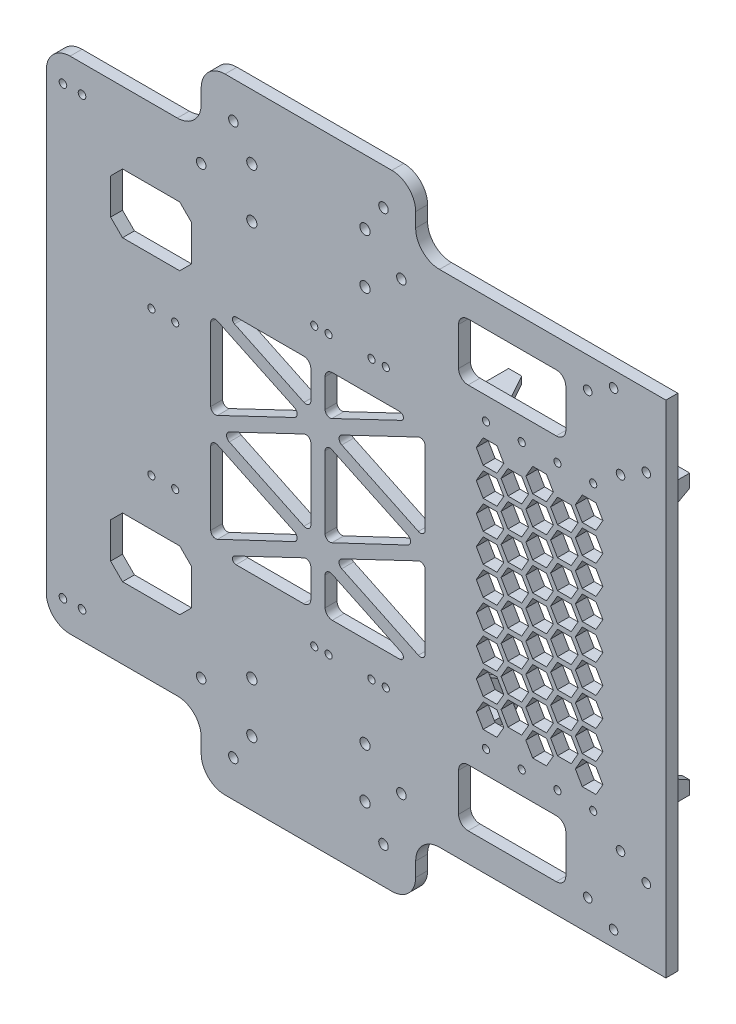
SolidWorks part; units mm, degrees
ref_plane "前视基准面" through (0, 0, 0) normal (0, 0, 1) x (1, 0, 0)
ref_plane "上视基准面" through (0, 0, 0) normal (0, 1, 0) x (1, 0, 0)
ref_plane "右视基准面" through (0, 0, 0) normal (1, 0, 0) x (0, 0, -1)
sketch "草图1" plane through (0, 0, 0) normal (0, 0, 1) x (1, 0, 0)
  line L2 (-130, 95) -> (-130, -95)
  line L3 (-120, -105) -> (-75, -105)
  line L4 (130, 95) -> (130, -95)
  line L5 (126.7518, 102.3765) -> (130, 105) construction
  line L6 (-130, -105) -> (-126.7518, -102.3765) construction
  line L9 (-65, -115) -> (-65, -121)
  line L10 (-55, -131) -> (15, -131)
  line L11 (25, -121) -> (25, -115)
  line L13 (35, -105) -> (120, -105)
  line L14 (126.7518, -102.3765) -> (130, -105) construction
  line L15 (-130, 105) -> (-126.7518, 102.3765) construction
  line L16 (-130, 0) -> (130, 0) construction
  line L17 (35, 105) -> (120, 105)
  line L18 (25, 121) -> (25, 115)
  line L19 (-55, 131) -> (15, 131)
  line L20 (-65, 115) -> (-65, 121)
  line L21 (-120, 105) -> (-75, 105)
  arc A1 (-120, -105) -> (-130, -95) centre (-120, -95) cw
  arc A3 (120, -105) -> (130, -95) centre (120, -95) ccw
  arc A8 (-65, -115) -> (-75, -105) centre (-75, -115) ccw
  arc A9 (25, -115) -> (35, -105) centre (35, -115) cw
  arc A10 (-55, -131) -> (-65, -121) centre (-55, -121) cw
  arc A11 (15, -131) -> (25, -121) centre (15, -121) ccw
  arc A12 (15, 131) -> (25, 121) centre (15, 121) cw
  arc A13 (-55, 131) -> (-65, 121) centre (-55, 121) ccw
  arc A14 (25, 115) -> (35, 105) centre (35, 115) ccw
  arc A15 (-65, 115) -> (-75, 105) centre (-75, 115) cw
  arc A16 (120, 105) -> (130, 95) centre (120, 95) cw
  arc A17 (-120, 105) -> (-130, 95) centre (-120, 95) ccw
  point P0 (0, 0)
  point P40 (25, -105)
  point P45 (25, 105)
  dimension "D2" = 10
  dimension "D3" = 65
  dimension "D4" = 10
  dimension "D5" = 105
  dimension "D7" = 10
  dimension "D8" = 10
  dimension "D10" = 10
  dimension "D12" = 10
  dimension "D13" = 105
  dimension "D18" = 90
  dimension "D19" = 6
extrude "凸台-拉伸1" add sketch "草图1" along normal blind 5
sketch "草图4" plane through (0, 0, 0) normal (0, 0, -1) x (-1, 0, 0)
  line L0 (-39, -47.5) -> (-39, -58.5)
  line L1 (-39, -58.5) -> (-50, -58.5)
  line L2 (-50, -58.5) -> (-50, -55.5)
  line L3 (-50, -55.5) -> (-42, -55.5)
  line L4 (-42, -55.5) -> (-42, -47.5)
  line L5 (-42, -47.5) -> (-39, -47.5)
  line L6 (-130, 0) -> (-25.5592, 0) construction
  line L7 (-130, -95) -> (-130, 95) construction
  line L10 (-130, -95) -> (-130, 95) construction
  dimension "D1" = 11
  dimension "D2" = 11
  dimension "D3" = 3
  dimension "D4" = 3
  dimension "D5" = 80
  dimension "D7" = 55.5
extrude "凸台-拉伸2" add sketch "草图4" along normal blind 20
sketch "草图5" plane through (0, -58.5, 0) normal (0, -1, 0) x (1, 0, 0)
  line L0 (50, -10) -> (44.5, -20)
  line L1 (50, -20) -> (50, 0) construction
  line L2 (50, -20) -> (39, -20) construction
  line L3 (44.5, -20) -> (50, -20)
  line L4 (50, -20) -> (50, -10)
  dimension "D1" = 10
  dimension "D2" = 5.5
extrude "切除-拉伸3" cut sketch "草图5" against normal blind 10
sketch "草图6" plane through (39, 0, 0) normal (-1, 0, 0) x (0, 0, 1)
  line L0 (-20, -53) -> (-10, -47.5)
  line L1 (-20, -58.5) -> (-20, -47.5) construction
  line L2 (-20, -47.5) -> (0, -47.5) construction
  line L3 (-10, -47.5) -> (-20, -47.5)
  line L4 (-20, -47.5) -> (-20, -53)
  dimension "D1" = 10
  dimension "D2" = 5.5
extrude "切除-拉伸4" cut sketch "草图6" against normal blind 10
ref_plane "基准面2" through (77, 0, 0) normal (1, 0, 0) x (0, 0, -1)
mirror "镜向1" about plane through (77, 0, 0) normal (1, 0, 0) of "凸台-拉伸2", "切除-拉伸4", "切除-拉伸3"
mirror "镜向2" about plane through (0, 0, 0) normal (0, 1, 0) of "镜向1"
sketch "草图7" plane through (0, 0, 0) normal (0, 0, -1) x (-1, 0, 0)
  line L4 (-112, -55.5) -> (-104, -55.5) construction
  line L5 (-112, 47.5) -> (-112, 55.5) construction
  line L6 (-112, 55.5) -> (-104, 55.5) construction
  line L7 (-92.013, 36) -> (-94.8997, 41)
  line L8 (-94.8997, 41) -> (-100.6732, 41)
  line L9 (-100.6732, 41) -> (-103.56, 36)
  line L10 (-103.56, 36) -> (-100.6732, 31)
  line L11 (-100.6732, 31) -> (-94.8997, 31)
  line L12 (-94.8997, 31) -> (-92.013, 36)
  line L13 (-77.0019, 36) -> (-97.7865, 36) construction
  line L14 (-74.1151, 31) -> (-71.2284, 36)
  line L15 (-71.2284, 36) -> (-74.1151, 41)
  line L16 (-74.1151, 41) -> (-79.8886, 41)
  line L17 (-79.8886, 41) -> (-82.7754, 36)
  line L18 (-82.7754, 36) -> (-79.8886, 31)
  line L19 (-79.8886, 31) -> (-74.1151, 31)
  line L20 (-92.013, 24) -> (-94.8997, 29)
  line L21 (-93.1677, 30) -> (-90.2809, 25)
  line L22 (-90.2809, 25) -> (-84.5074, 25)
  line L23 (-84.5074, 25) -> (-81.6207, 30)
  line L24 (-81.6207, 30) -> (-84.5074, 35)
  line L25 (-84.5074, 35) -> (-90.2809, 35)
  line L26 (-90.2809, 35) -> (-93.1677, 30)
  line L27 (-84.5074, 37) -> (-81.6207, 42)
  line L28 (-81.6207, 42) -> (-84.5074, 47)
  line L29 (-84.5074, 47) -> (-90.2809, 47)
  line L30 (-90.2809, 47) -> (-93.1677, 42)
  line L31 (-93.1677, 42) -> (-90.2809, 37)
  line L32 (-90.2809, 37) -> (-84.5074, 37)
  line L33 (-79.8886, 43) -> (-74.1151, 43)
  line L34 (-74.1151, 43) -> (-71.2284, 48)
  line L35 (-71.2284, 48) -> (-74.1151, 53)
  line L36 (-74.1151, 53) -> (-79.8886, 53)
  line L37 (-79.8886, 53) -> (-82.7754, 48)
  line L38 (-82.7754, 48) -> (-79.8886, 43)
  line L39 (-94.8997, 43) -> (-92.013, 48)
  line L40 (-92.013, 48) -> (-94.8997, 53)
  line L41 (-94.8997, 53) -> (-100.6732, 53)
  line L42 (-100.6732, 53) -> (-103.56, 48)
  line L43 (-103.56, 48) -> (-100.6732, 43)
  line L44 (-100.6732, 43) -> (-94.8997, 43)
  line L45 (-72.3831, 42) -> (-69.4963, 37)
  line L46 (-69.4963, 37) -> (-63.7228, 37)
  line L47 (-63.7228, 37) -> (-60.8361, 42)
  line L48 (-60.8361, 42) -> (-63.7228, 47)
  line L49 (-63.7228, 47) -> (-69.4963, 47)
  line L50 (-69.4963, 47) -> (-72.3831, 42)
  line L51 (-94.8997, 29) -> (-100.6732, 29)
  line L52 (-100.6732, 29) -> (-103.56, 24)
  line L53 (-103.56, 24) -> (-100.6732, 19)
  line L54 (-100.6732, 19) -> (-94.8997, 19)
  line L55 (-94.8997, 19) -> (-92.013, 24)
  line L56 (-93.1677, 18) -> (-90.2809, 13)
  line L57 (-90.2809, 13) -> (-84.5074, 13)
  line L58 (-84.5074, 13) -> (-81.6207, 18)
  line L59 (-81.6207, 18) -> (-84.5074, 23)
  line L60 (-84.5074, 23) -> (-90.2809, 23)
  line L61 (-90.2809, 23) -> (-93.1677, 18)
  line L62 (-74.1151, 19) -> (-71.2284, 24)
  line L63 (-71.2284, 24) -> (-74.1151, 29)
  line L64 (-74.1151, 29) -> (-79.8886, 29)
  line L65 (-79.8886, 29) -> (-82.7754, 24)
  line L66 (-82.7754, 24) -> (-79.8886, 19)
  line L67 (-79.8886, 19) -> (-74.1151, 19)
  line L68 (-72.3831, 30) -> (-69.4963, 25)
  line L69 (-69.4963, 25) -> (-63.7228, 25)
  line L70 (-63.7228, 25) -> (-60.8361, 30)
  line L71 (-60.8361, 30) -> (-63.7228, 35)
  line L72 (-63.7228, 35) -> (-69.4963, 35)
  line L73 (-69.4963, 35) -> (-72.3831, 30)
  line L74 (-92.013, 12) -> (-94.8997, 17)
  line L75 (-94.8997, 17) -> (-100.6732, 17)
  line L76 (-100.6732, 17) -> (-103.56, 12)
  line L77 (-103.56, 12) -> (-100.6732, 7)
  line L78 (-100.6732, 7) -> (-94.8997, 7)
  line L79 (-94.8997, 7) -> (-92.013, 12)
  line L80 (-93.1677, 6) -> (-90.2809, 1)
  line L81 (-90.2809, 1) -> (-84.5074, 1)
  line L82 (-84.5074, 1) -> (-81.6207, 6)
  line L83 (-81.6207, 6) -> (-84.5074, 11)
  line L84 (-84.5074, 11) -> (-90.2809, 11)
  line L85 (-90.2809, 11) -> (-93.1677, 6)
  line L86 (-74.1151, 7) -> (-71.2284, 12)
  line L87 (-71.2284, 12) -> (-74.1151, 17)
  line L88 (-74.1151, 17) -> (-79.8886, 17)
  line L89 (-79.8886, 17) -> (-82.7754, 12)
  line L90 (-82.7754, 12) -> (-79.8886, 7)
  line L91 (-79.8886, 7) -> (-74.1151, 7)
  line L92 (-72.3831, 18) -> (-69.4963, 13)
  line L93 (-69.4963, 13) -> (-63.7228, 13)
  line L94 (-63.7228, 13) -> (-60.8361, 18)
  line L95 (-60.8361, 18) -> (-63.7228, 23)
  line L96 (-63.7228, 23) -> (-69.4963, 23)
  line L97 (-69.4963, 23) -> (-72.3831, 18)
  line L98 (-92.013, 0) -> (-94.8997, 5)
  line L99 (-94.8997, 5) -> (-100.6732, 5)
  line L100 (-100.6732, 5) -> (-103.56, 0)
  line L101 (-103.56, 0) -> (-100.6732, -5)
  line L102 (-100.6732, -5) -> (-94.8997, -5)
  line L103 (-94.8997, -5) -> (-92.013, 0)
  line L104 (-93.1677, -6) -> (-90.2809, -11)
  line L105 (-90.2809, -11) -> (-84.5074, -11)
  line L106 (-84.5074, -11) -> (-81.6207, -6)
  line L107 (-81.6207, -6) -> (-84.5074, -1)
  line L108 (-84.5074, -1) -> (-90.2809, -1)
  line L109 (-90.2809, -1) -> (-93.1677, -6)
  line L110 (-74.1151, -5) -> (-71.2284, 0)
  line L111 (-71.2284, 0) -> (-74.1151, 5)
  line L112 (-74.1151, 5) -> (-79.8886, 5)
  line L113 (-79.8886, 5) -> (-82.7754, 0)
  line L114 (-82.7754, 0) -> (-79.8886, -5)
  line L115 (-79.8886, -5) -> (-74.1151, -5)
  line L116 (-72.3831, 6) -> (-69.4963, 1)
  line L117 (-69.4963, 1) -> (-63.7228, 1)
  line L118 (-63.7228, 1) -> (-60.8361, 6)
  line L119 (-60.8361, 6) -> (-63.7228, 11)
  line L120 (-63.7228, 11) -> (-69.4963, 11)
  line L121 (-69.4963, 11) -> (-72.3831, 6)
  line L122 (-92.013, -12) -> (-94.8997, -7)
  line L123 (-94.8997, -7) -> (-100.6732, -7)
  line L124 (-100.6732, -7) -> (-103.56, -12)
  line L125 (-103.56, -12) -> (-100.6732, -17)
  line L126 (-100.6732, -17) -> (-94.8997, -17)
  line L127 (-94.8997, -17) -> (-92.013, -12)
  line L128 (-93.1677, -18) -> (-90.2809, -23)
  line L129 (-90.2809, -23) -> (-84.5074, -23)
  line L130 (-84.5074, -23) -> (-81.6207, -18)
  line L131 (-81.6207, -18) -> (-84.5074, -13)
  line L132 (-84.5074, -13) -> (-90.2809, -13)
  line L133 (-90.2809, -13) -> (-93.1677, -18)
  line L134 (-74.1151, -17) -> (-71.2284, -12)
  line L135 (-71.2284, -12) -> (-74.1151, -7)
  line L136 (-74.1151, -7) -> (-79.8886, -7)
  line L137 (-79.8886, -7) -> (-82.7754, -12)
  line L138 (-82.7754, -12) -> (-79.8886, -17)
  line L139 (-79.8886, -17) -> (-74.1151, -17)
  line L140 (-72.3831, -6) -> (-69.4963, -11)
  line L141 (-69.4963, -11) -> (-63.7228, -11)
  line L142 (-63.7228, -11) -> (-60.8361, -6)
  line L143 (-60.8361, -6) -> (-63.7228, -1)
  line L144 (-63.7228, -1) -> (-69.4963, -1)
  line L145 (-69.4963, -1) -> (-72.3831, -6)
  line L146 (-92.013, -24) -> (-94.8997, -19)
  line L147 (-94.8997, -19) -> (-100.6732, -19)
  line L148 (-100.6732, -19) -> (-103.56, -24)
  line L149 (-103.56, -24) -> (-100.6732, -29)
  line L150 (-100.6732, -29) -> (-94.8997, -29)
  line L151 (-94.8997, -29) -> (-92.013, -24)
  line L152 (-93.1677, -30) -> (-90.2809, -35)
  line L153 (-90.2809, -35) -> (-84.5074, -35)
  line L154 (-84.5074, -35) -> (-81.6207, -30)
  line L155 (-81.6207, -30) -> (-84.5074, -25)
  line L156 (-84.5074, -25) -> (-90.2809, -25)
  line L157 (-90.2809, -25) -> (-93.1677, -30)
  line L158 (-74.1151, -29) -> (-71.2284, -24)
  line L159 (-71.2284, -24) -> (-74.1151, -19)
  line L160 (-74.1151, -19) -> (-79.8886, -19)
  line L161 (-79.8886, -19) -> (-82.7754, -24)
  line L162 (-82.7754, -24) -> (-79.8886, -29)
  line L163 (-79.8886, -29) -> (-74.1151, -29)
  line L164 (-72.3831, -18) -> (-69.4963, -23)
  line L165 (-69.4963, -23) -> (-63.7228, -23)
  line L166 (-63.7228, -23) -> (-60.8361, -18)
  line L167 (-60.8361, -18) -> (-63.7228, -13)
  line L168 (-63.7228, -13) -> (-69.4963, -13)
  line L169 (-69.4963, -13) -> (-72.3831, -18)
  line L170 (-92.013, -36) -> (-94.8997, -31)
  line L171 (-94.8997, -31) -> (-100.6732, -31)
  line L172 (-100.6732, -31) -> (-103.56, -36)
  line L173 (-103.56, -36) -> (-100.6732, -41)
  line L174 (-100.6732, -41) -> (-94.8997, -41)
  line L175 (-94.8997, -41) -> (-92.013, -36)
  line L176 (-93.1677, -42) -> (-90.2809, -47)
  line L177 (-90.2809, -47) -> (-84.5074, -47)
  line L178 (-84.5074, -47) -> (-81.6207, -42)
  line L179 (-81.6207, -42) -> (-84.5074, -37)
  line L180 (-84.5074, -37) -> (-90.2809, -37)
  line L181 (-90.2809, -37) -> (-93.1677, -42)
  line L182 (-74.1151, -41) -> (-71.2284, -36)
  line L183 (-71.2284, -36) -> (-74.1151, -31)
  line L184 (-74.1151, -31) -> (-79.8886, -31)
  line L185 (-79.8886, -31) -> (-82.7754, -36)
  line L186 (-82.7754, -36) -> (-79.8886, -41)
  line L187 (-79.8886, -41) -> (-74.1151, -41)
  line L188 (-72.3831, -30) -> (-69.4963, -35)
  line L189 (-69.4963, -35) -> (-63.7228, -35)
  line L190 (-63.7228, -35) -> (-60.8361, -30)
  line L191 (-60.8361, -30) -> (-63.7228, -25)
  line L192 (-63.7228, -25) -> (-69.4963, -25)
  line L193 (-69.4963, -25) -> (-72.3831, -30)
  line L194 (-92.013, -48) -> (-94.8997, -43)
  line L195 (-94.8997, -43) -> (-100.6732, -43)
  line L196 (-100.6732, -43) -> (-103.56, -48)
  line L197 (-103.56, -48) -> (-100.6732, -53)
  line L198 (-100.6732, -53) -> (-94.8997, -53)
  line L199 (-94.8997, -53) -> (-92.013, -48)
  line L206 (-74.1151, -53) -> (-71.2284, -48)
  line L207 (-71.2284, -48) -> (-74.1151, -43)
  line L208 (-74.1151, -43) -> (-79.8886, -43)
  line L209 (-79.8886, -43) -> (-82.7754, -48)
  line L210 (-82.7754, -48) -> (-79.8886, -53)
  line L211 (-79.8886, -53) -> (-74.1151, -53)
  line L212 (-72.3831, -42) -> (-69.4963, -47)
  line L213 (-69.4963, -47) -> (-63.7228, -47)
  line L214 (-63.7228, -47) -> (-60.8361, -42)
  line L215 (-60.8361, -42) -> (-63.7228, -37)
  line L216 (-63.7228, -37) -> (-69.4963, -37)
  line L217 (-69.4963, -37) -> (-72.3831, -42)
  line L218 (-61.9908, 36) -> (-59.104, 31)
  line L219 (-61.9908, 48) -> (-59.104, 43)
  line L220 (-59.104, 43) -> (-53.3305, 43)
  line L221 (-53.3305, 43) -> (-50.4438, 48)
  line L222 (-50.4438, 48) -> (-53.3305, 53)
  line L223 (-53.3305, 53) -> (-59.104, 53)
  line L224 (-59.104, 53) -> (-61.9908, 48)
  line L225 (-59.104, 31) -> (-53.3305, 31)
  line L226 (-53.3305, 31) -> (-50.4438, 36)
  line L227 (-50.4438, 36) -> (-53.3305, 41)
  line L228 (-53.3305, 41) -> (-59.104, 41)
  line L229 (-59.104, 41) -> (-61.9908, 36)
  line L230 (-61.9908, 24) -> (-59.104, 19)
  line L231 (-59.104, 19) -> (-53.3305, 19)
  line L232 (-53.3305, 19) -> (-50.4438, 24)
  line L233 (-50.4438, 24) -> (-53.3305, 29)
  line L234 (-53.3305, 29) -> (-59.104, 29)
  line L235 (-59.104, 29) -> (-61.9908, 24)
  line L236 (-61.9908, 12) -> (-59.104, 7)
  line L237 (-59.104, 7) -> (-53.3305, 7)
  line L238 (-53.3305, 7) -> (-50.4438, 12)
  line L239 (-50.4438, 12) -> (-53.3305, 17)
  line L240 (-53.3305, 17) -> (-59.104, 17)
  line L241 (-59.104, 17) -> (-61.9908, 12)
  line L242 (-61.9908, 0) -> (-59.104, -5)
  line L243 (-59.104, -5) -> (-53.3305, -5)
  line L244 (-53.3305, -5) -> (-50.4438, 0)
  line L245 (-50.4438, 0) -> (-53.3305, 5)
  line L246 (-53.3305, 5) -> (-59.104, 5)
  line L247 (-59.104, 5) -> (-61.9908, 0)
  line L248 (-61.9908, -12) -> (-59.104, -17)
  line L249 (-59.104, -17) -> (-53.3305, -17)
  line L250 (-53.3305, -17) -> (-50.4438, -12)
  line L251 (-50.4438, -12) -> (-53.3305, -7)
  line L252 (-53.3305, -7) -> (-59.104, -7)
  line L253 (-59.104, -7) -> (-61.9908, -12)
  line L254 (-61.9908, -24) -> (-59.104, -29)
  line L255 (-59.104, -29) -> (-53.3305, -29)
  line L256 (-53.3305, -29) -> (-50.4438, -24)
  line L257 (-50.4438, -24) -> (-53.3305, -19)
  line L258 (-53.3305, -19) -> (-59.104, -19)
  line L259 (-59.104, -19) -> (-61.9908, -24)
  line L260 (-61.9908, -36) -> (-59.104, -41)
  line L261 (-59.104, -41) -> (-53.3305, -41)
  line L262 (-53.3305, -41) -> (-50.4438, -36)
  line L263 (-50.4438, -36) -> (-53.3305, -31)
  line L264 (-53.3305, -31) -> (-59.104, -31)
  line L265 (-59.104, -31) -> (-61.9908, -36)
  line L266 (-61.9908, -48) -> (-59.104, -53)
  line L267 (-59.104, -53) -> (-53.3305, -53)
  line L268 (-53.3305, -53) -> (-50.4438, -48)
  line L269 (-50.4438, -48) -> (-53.3305, -43)
  line L270 (-53.3305, -43) -> (-59.104, -43)
  line L271 (-59.104, -43) -> (-61.9908, -48)
  line L272 (-93.1677, -54) -> (-90.2809, -59) [skipped]
  line L273 (-90.2809, -59) -> (-84.5074, -59) [skipped]
  line L274 (-84.5074, -59) -> (-81.6207, -54) [skipped]
  line L275 (-81.6207, -54) -> (-84.5074, -49) [skipped]
  line L276 (-84.5074, -49) -> (-90.2809, -49) [skipped]
  line L277 (-90.2809, -49) -> (-93.1677, -54) [skipped]
  circle A0 centre (-97.7865, 36) radius 5 construction
  circle A1 centre (-77.0019, 36) radius 5 construction
  circle A2 centre (-87.3942, 30) radius 5 construction
  circle A3 centre (-87.3942, 42) radius 5 construction
  circle A4 centre (-77.0019, 48) radius 5 construction
  circle A5 centre (-97.7865, 48) radius 5 construction
  circle A6 centre (-66.6096, 42) radius 5 construction
  circle A7 centre (-56.2173, 48) radius 5 construction
  point P4 (-87.3942, 37)
  dimension "D1" = 2
  dimension "D3" = 10
  dimension "D4" = 10
  dimension "D5" = 2
  dimension "D7" = 10
  dimension "D11" = 10
  dimension "D14" = 10
  dimension "D15" = 10
  dimension "D20" = 10
  dimension "D2" = 2
  dimension "D6" = 2
  dimension "D8" = 2
  dimension "D9" = 2
  dimension "D10" = 2
  dimension "D12" = 2
  dimension "D13" = 2
  dimension "D16" = 2
  dimension "D17" = 2
  dimension "D19" = 2
  dimension "D21" = 9
  dimension "D22" = 2.5
  dimension "D23" = 2.5
  dimension "D24" = 8.44
  dimension "D18" = 8
extrude "切除-拉伸5" cut sketch "草图7" against normal blind 5
sketch "草图8" plane through (0, 0, 0) normal (0, 0, -1) x (-1, 0, 0)
  line L0 (-75.3677, 120) -> (-75.3677, -120)
  line L1 (-100.0285, 77.2863) -> (-100.0285, -77.2863)
  line L2 (-100.0285, 77.2863) -> (-75.3677, 120)
  line L3 (-100.0285, -77.2863) -> (-75.3677, -120)
  line L4 (-37.1297, 0) -> (-146.8562, 0) construction
  dimension "D1" = 30
  dimension "D2" = 30
  dimension "D3" = 120
  dimension "D4" = 120
sketch "草图9" plane through (0, 0, 0) normal (0, 0, -1) x (-1, 0, 0)
  line L0 (148.8518, 0) -> (-37.1297, 0) construction
  line L1 (-29, 41) -> (-29, 4)
  line L2 (-25, -45) -> (13, -45)
  line L3 (61, -41) -> (61, -4)
  line L4 (57, 45) -> (19, 45)
  line L14 (-29, 41) -> (9.8049, 22.5)
  line L15 (57, 0) -> (19, -18.1163)
  line L16 (130, 95) -> (130, -95) construction
  line L17 (63, 93) -> (118, 93)
  line L18 (63, 93) -> (63, 66)
  line L19 (63, 66) -> (118, 66)
  line L20 (118, 93) -> (118, 66)
  line L21 (75, 105) -> (120, 105) construction
  line L22 (63, -66) -> (118, -66)
  line L23 (118, -93) -> (118, -66)
  line L24 (63, -93) -> (118, -93)
  line L25 (63, -93) -> (63, -66)
  line L26 (-120, 105) -> (-35, 105) construction
  line L27 (-43, 93) -> (-88, 93)
  line L28 (-43, 93) -> (-43, 69)
  line L29 (-43, 69) -> (-88, 69)
  line L30 (-88, 93) -> (-88, 69)
  line L31 (-130, -95) -> (-130, 95) construction
  line L32 (-43, -69) -> (-88, -69)
  line L33 (-88, -93) -> (-88, -69)
  line L34 (-43, -93) -> (-88, -93)
  line L35 (-43, -93) -> (-43, -69)
  line L36 (-25, 45) -> (13, 26.8837)
  line L37 (-25, -45) -> (13, -26.8837)
  line L38 (61, 41) -> (22.0746, 22.5575)
  line L39 (-25.5359, 0) -> (13, -18.258)
  line L40 (57, 45) -> (19, 26.8837)
  line L41 (57, -45) -> (19, -26.8837)
  line L42 (16, 61.4977) -> (16, -60.5731) construction
  line L43 (13, 45) -> (13, 26.8837)
  line L44 (19, 45) -> (19, 26.8837)
  line L45 (13, 18.258) -> (13, -18.258)
  line L46 (9.8049, 22.5) -> (-29, 4)
  line L47 (19, 18.1163) -> (57, 0)
  line L48 (22.0746, 22.5575) -> (61, 4)
  line L49 (13, 18.258) -> (-25.5359, 0)
  line L50 (19, 18.1163) -> (19, -18.1163)
  line L51 (22.0746, -22.5575) -> (61, -41)
  line L52 (9.8049, -22.5) -> (-29, -41)
  line L53 (9.8049, -22.5) -> (-29, -4)
  line L54 (22.0746, -22.5575) -> (61, -4)
  line L55 (13, -26.8837) -> (13, -45)
  line L56 (19, -26.8837) -> (19, -45)
  line L57 (13, 45) -> (-25, 45)
  line L58 (-29, -4) -> (-29, -41)
  line L59 (19, -45) -> (57, -45)
  line L60 (61, 4) -> (61, 41)
  line L61 (-44, 41) -> (-44, -37.8122) construction
  dimension "D1" = 45
  dimension "D2" = 45
  dimension "D3" = 15
  dimension "D4" = 90
  dimension "D5" = 1
  dimension "D7" = 12
  dimension "D8" = 12
  dimension "D9" = 27
  dimension "D10" = 55
  dimension "D11" = 12
  dimension "D12" = 45
  dimension "D13" = 42
  dimension "D14" = 24
  dimension "D21" = 4
  dimension "D22" = 4
  dimension "D23" = 4
  dimension "D24" = 4
  dimension "D26" = 4
  dimension "D27" = 3
  dimension "D28" = 45
extrude "切除-拉伸6" cut sketch "草图9" against normal blind 5 contours L27 L30 L29 L28 | L34 L35 L32 L33 | L4 L44 L40 | L48 L60 L38 | L47 L50 L15 | L54 L51 L3 | L56 L59 L41 | L55 L37 L2 | L53 L58 L52 | L45 L49 L39 | L46 L14 L1 | L43 L57 L36 | L57 L36 L43 region at (16.065, 22.5, 0) region at (-0.3333, -38.9612, 0) region at (-48.0249, -22.5192, 0) region at (-31.6667, 38.9612, 0) region at (-31.6667, 0, 0) region at (65.5, 81, 0) region at (65.5, -81, 0) region at (-0.3333, 38.9612, 0) region at (-48.0249, 22.5192, 0) region at (-0.1547, 0, 0) region at (-31.6667, -38.9612, 0) region at (16.065, -22.5, 0)
fillet "圆角1" radius 4 8 edges at (43, -93, 2.5) (88, -69, 2.5) (43, -69, 2.5) (88, -93, 2.5) (88, 69, 2.5) (43, 69, 2.5) (43, 93, 2.5) (88, 93, 2.5)
fillet "圆角2" radius 1.5 4 edges at (25, -45, 2.5) (-57, -45, 2.5) (25, 45, 2.5) (-57, 45, 2.5)
fillet "圆角3" radius 2 22 edges at (29, -4, 2.5) (29, 4, 2.5) (-13, -18.258, 2.5) (-61, -41, 2.5) (-61, 4, 2.5) (-13, -26.8837, 2.5) (-13, 18.258, 2.5) (-61, -4, 2.5) (-22.0746, -22.5575, 2.5) (25.5359, 0, 2.5) (-22.0746, 22.5575, 2.5) (-61, 41, 2.5) (-19, 26.8837, 2.5) (-19, -26.8837, 2.5) (-19, -18.1163, 2.5) (29, -41, 2.5) (29, 41, 2.5) (-57, 0, 2.5) (-9.8049, -22.5, 2.5) (-13, 26.8837, 2.5) (-9.8049, 22.5, 2.5) (-19, 18.1163, 2.5)
fillet "圆角4" radius 3 4 edges at (-13, -45, 2.5) (-13, 45, 2.5) (-19, -45, 2.5) (-19, 45, 2.5)
sketch "草图12" plane through (0, 0, 0) normal (0, 0, -1) x (-1, 0, 0)
  line L1 (-120, 105) -> (-130, 105)
  line L2 (-120, 105) -> (-120, -105)
  line L3 (-120, -105) -> (-130, -105)
  line L4 (-130, 105) -> (-130, -105)
extrude "凸台-拉伸3" add sketch "草图12" against normal up to surface (5 mm away) up to face at (65.5, 81, 5)
sketch "草图10" plane through (0, 0, 0) normal (0, 0, -1) x (-1, 0, 0)
  line L0 (-37.1297, 0) -> (-146.8562, 0) construction
  line L1 (-37.1297, 0) -> (-146.8562, 0) construction
  circle A0 centre (-121.782, 74.6081) radius 1.8 construction
  circle A1 centre (-110.9567, 68.3581) radius 1.8 construction
  circle A2 centre (-108.032, 98.4238) radius 1.8 construction
  circle A3 centre (-97.2067, 92.1738) radius 1.8 construction
  circle A4 centre (-3.75, 104) radius 2.15 construction
  circle A5 centre (-3.75, 104) radius 2.15
  circle A6 centre (-3.75, -104) radius 2.15
  circle A7 centre (115, 93.5) radius 1.6 construction
  circle A8 centre (123, 93.5) radius 1.6 construction
  circle A9 centre (115, 93.5) radius 1.6
  circle A10 centre (123, 93.5) radius 1.6
  circle A11 centre (123, -93.5) radius 1.6
  circle A12 centre (115, -93.5) radius 1.6
  circle A15 centre (-121.782, 74.6081) radius 1.8
  circle A16 centre (-110.9567, 68.3581) radius 1.8
  circle A17 centre (-108.032, 98.4238) radius 1.8
  circle A18 centre (-97.2067, 92.1738) radius 1.8
  circle A41 centre (-97.2067, -92.1738) radius 1.8
  circle A42 centre (-108.032, -98.4238) radius 1.8
  circle A43 centre (-110.9567, -68.3581) radius 1.8
  circle A44 centre (-121.782, -74.6081) radius 1.8
  circle A45 centre (-99.5, 59.5) radius 1.5 construction
  circle A46 centre (-84.5, 59.5) radius 1.5 construction
  circle A47 centre (-69.5, 59.5) radius 1.5 construction
  circle A48 centre (-54.5, 59.5) radius 1.5 construction
  circle A49 centre (-12.4571, 58.25) radius 1.5 construction
  circle A50 centre (-6.4571, 58.25) radius 1.5 construction
  circle A51 centre (11.5429, 58.25) radius 1.5 construction
  circle A52 centre (17.5429, 58.25) radius 1.5 construction
  circle A53 centre (-99.5, 59.5) radius 1.5
  circle A54 centre (-84.5, 59.5) radius 1.5
  circle A55 centre (-69.5, 59.5) radius 1.5
  circle A56 centre (-54.5, 59.5) radius 1.5
  circle A57 centre (-12.4571, 58.25) radius 1.5
  circle A58 centre (-6.4571, 58.25) radius 1.5
  circle A59 centre (11.5429, 58.25) radius 1.5
  circle A60 centre (17.5429, 58.25) radius 1.5
  circle A61 centre (17.5429, -58.25) radius 1.5
  circle A62 centre (11.5429, -58.25) radius 1.5
  circle A63 centre (-6.4571, -58.25) radius 1.5
  circle A64 centre (-12.4571, -58.25) radius 1.5
  circle A65 centre (-54.5, -59.5) radius 1.5
  circle A66 centre (-69.5, -59.5) radius 1.5
  circle A67 centre (-84.5, -59.5) radius 1.5
  circle A68 centre (-99.5, -59.5) radius 1.5
  circle A89 centre (75.897, 30.3) radius 1.5 construction
  circle A90 centre (85.897, 30.3) radius 1.5 construction
  circle A91 centre (75.897, 30.3) radius 1.5
  circle A92 centre (85.897, 30.3) radius 1.5
  circle A93 centre (85.897, -30.3) radius 1.5
  circle A94 centre (75.897, -30.3) radius 1.5
  circle A95 centre (43.75, 83) radius 2.15 construction
  circle A96 centre (43.75, 104) radius 2.15 construction
  circle A97 centre (-3.75, 83) radius 2.15 construction
  circle A99 centre (43.75, 83) radius 2.15
  circle A100 centre (43.75, 104) radius 2.15
  circle A101 centre (-3.75, 83) radius 2.15
  circle A104 centre (-3.75, -83) radius 2.15
  circle A105 centre (43.75, -104) radius 2.15
  circle A106 centre (43.75, -83) radius 2.15
extrude "切除-拉伸7" cut sketch "草图10" against normal through all
sketch "草图11" plane through (0, 0, 0) normal (0, 0, -1) x (-1, 0, 0)
  line L0 (130, 95) -> (130, -95) construction
  line L1 (74, -75) -> (98, -75)
  line L2 (69, -70) -> (69, -55)
  line L3 (74, -50) -> (98, -50)
  line L4 (103, -70) -> (103, -55)
  line L5 (130, 0) -> (108.529, 0) construction
  line L10 (69, -70) -> (74, -75)
  line L11 (69, -55) -> (74, -50)
  line L12 (98, -50) -> (103, -55)
  line L13 (98, -75) -> (103, -70)
  line L14 (98, 75) -> (103, 70)
  line L15 (98, 50) -> (103, 55)
  line L16 (69, 55) -> (74, 50)
  line L17 (69, 70) -> (74, 75)
  line L18 (103, 70) -> (103, 55)
  line L19 (74, 50) -> (98, 50)
  line L20 (69, 70) -> (69, 55)
  line L21 (74, 75) -> (98, 75)
  point P0 (69, -75)
  point P1 (103, -50)
  point P2 (69, -50)
  point P3 (103, -75)
  point P8 (103, 75)
  point P9 (69, 50)
  point P10 (103, 50)
  point P11 (69, 75)
  dimension "D1" = 34
  dimension "D2" = 25
  dimension "D3" = 27
  dimension "D4" = 50
extrude "切除-拉伸8" cut sketch "草图11" against normal through all
sketch "草图14" plane through (0, 0, 5) normal (0, 0, 1) x (1, 0, 0)
  line L0 (25, -121) -> (25, -115) construction
  line L1 (-55, -131) -> (15, -131) construction
  line L2 (-20, -131) -> (-20, 131) construction
  line L3 (15, 131) -> (-55, 131) construction
  line L4 (-20, 0) -> (-130, 0) construction
  line L5 (-130, 95) -> (-130, -95) construction
  circle A0 centre (11.5, -115.68) radius 2
  circle A1 centre (-51.5, -115.68) radius 2
  circle A2 centre (-51.5, 115.68) radius 2
  circle A3 centre (11.5, 115.68) radius 2
  dimension "D1" = 4
  dimension "D2" = 13.5
  dimension "D3" = 15.32
extrude "切除-拉伸9" cut sketch "草图14" against normal blind 10
sketch "草图15" plane through (0, 0, 0) normal (0, 0, -1) x (-1, 0, 0)
  line L0 (65, -93.5) -> (-19, -93.5) construction
  line L1 (130, 0) -> (-85.2757, 0) construction
  line L2 (130, 95) -> (130, -95) construction
  line L3 (-25, -121) -> (-25, -115) construction
  circle A0 centre (65, -93.5) radius 2
  circle A1 centre (-19, -93.5) radius 2
  circle A2 centre (65, 93.5) radius 2
  circle A3 centre (-19, 93.5) radius 2
  dimension "D1" = 4
  dimension "D3" = 6
  dimension "D2" = 84
extrude "切除-拉伸10" cut sketch "草图15" against normal through all
equation "\"45、\"=43.7672"
